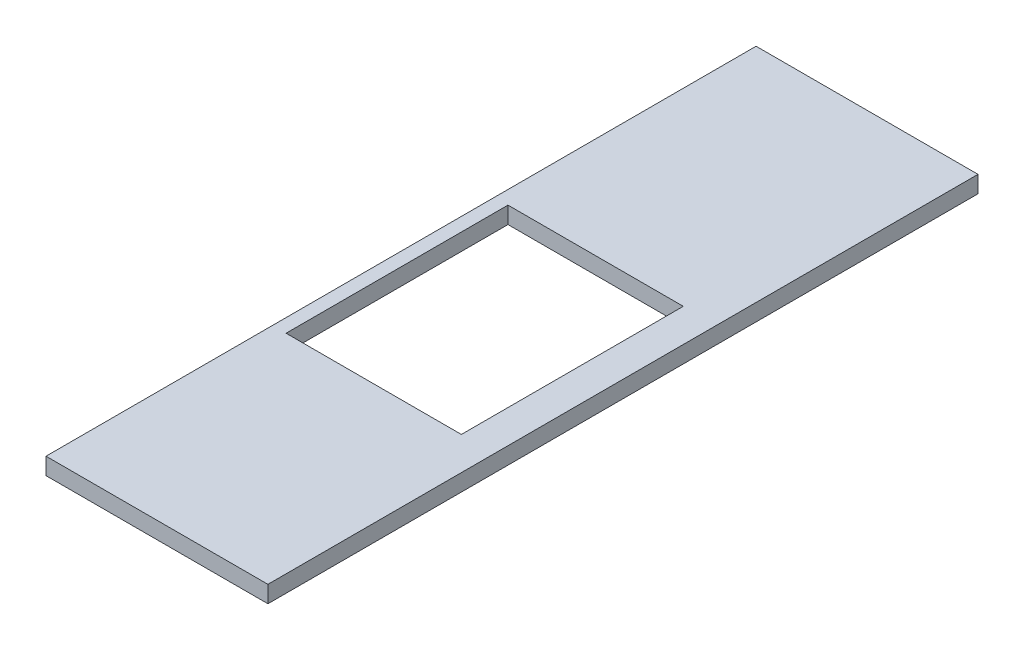
SolidWorks part; units mm, degrees
ref_plane "Спереди" through (0, 0, 0) normal (0, 0, 1) x (1, 0, 0)
ref_plane "Сверху" through (0, 0, 0) normal (0, 1, 0) x (1, 0, 0)
ref_plane "Справа" through (0, 0, 0) normal (1, 0, 0) x (0, 0, -1)
sketch "Эскиз1" plane through (0, 0, 0) normal (0, 1, 0) x (1, 0, 0)
  line L0 (0, 0) -> (0, 1600)
  line L1 (0, 1600) -> (500, 1600)
  line L2 (500, 1600) -> (500, 0)
  line L5 (500, 0) -> (0, 0)
  point P3 (0, 0)
  point P6 (1630, -930)
  point P8 (1151.5678, 0)
  dimension "D1" = 500
  dimension "D2" = 1600
extrude "Бобышка-Вытянуть1" add sketch "Эскиз1" along normal blind 38
sketch "Эскиз2" plane through (0, 38, 0) normal (0, 1, 0) x (1, 0, 0)
  line L1 (30.511, 1010.4113) -> (425.511, 1010.4113)
  line L2 (30.511, 1010.4113) -> (30.511, 510.4113)
  line L3 (30.511, 510.4113) -> (425.511, 510.4113)
  line L4 (425.511, 1010.4113) -> (425.511, 510.4113)
extrude "Вырез-Вытянуть1" cut sketch "Эскиз2" against normal through all
